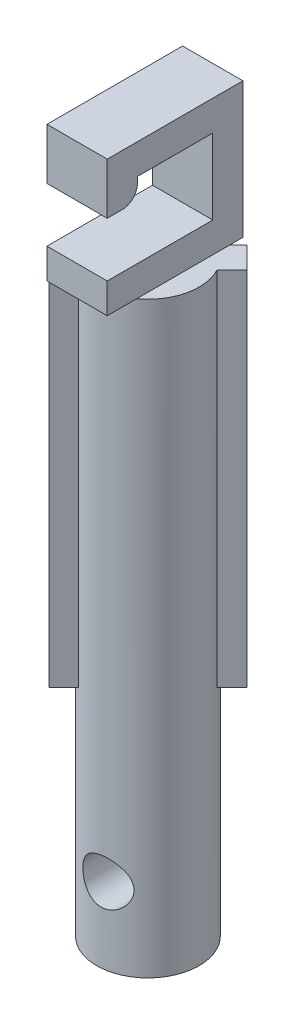
SolidWorks part; units mm, degrees
material "Plain Carbon Steel"
ref_plane "Front Plane" through (0, 0, 0) normal (0, 0, 1) x (1, 0, 0)
ref_plane "Top Plane" through (0, 0, 0) normal (0, 1, 0) x (1, 0, 0)
ref_plane "Right Plane" through (0, 0, 0) normal (1, 0, 0) x (0, 0, -1)
sketch "Sketch1" plane through (0, 0, 0) normal (0, 1, 0) x (1, 0, 0)
  circle A0 centre (0, 0) radius 1.7
  dimension "D1" = 3.4
extrude "main shaft" add sketch "Sketch1" along normal mid plane 12
sketch "Sketch2" plane through (0, 6, 0) normal (0, 1, 0) x (1, 0, 0)
  line L0 (3.2385, 3.2385) -> (-4.1755, -4.1755) construction
  line L1 (-0.7954, -1.5025) -> (-1.2903, -1.9974)
  line L2 (-1.2903, -1.9974) -> (-1.9974, -1.2903)
  line L3 (-1.9974, -1.2903) -> (-1.5025, -0.7954)
  line L4 (-1.9627, 1.9627) -> (2.0335, -2.0335) construction
  line L5 (1.2903, 1.9974) -> (0.7954, 1.5025)
  line L6 (1.9974, 1.2903) -> (1.2903, 1.9974)
  line L7 (1.5025, 0.7954) -> (1.9974, 1.2903)
  arc A0 (-1.5025, -0.7954) -> (-0.7954, -1.5025) centre (0, 0) ccw
  arc A1 (0.7954, 1.5025) -> (1.5025, 0.7954) centre (0, 0) cw
  circle A2 centre (0, 0) radius 1.7 construction
  point P8 (-1.0428, -1.75)
  dimension "D1" = 1
  dimension "D2" = 0.7
extrude "guides" add sketch "Sketch2" against normal blind 12
sketch "Sketch21" plane through (0, 6, 0) normal (0, 1, 0) x (1, 0, 0)
  line L0 (0, 0) -> (0, -1.7) construction
  line L1 (-1, 2.15) -> (1, 2.15)
  line L2 (-1, 2.15) -> (-1, -2.35)
  line L3 (-1, -2.35) -> (1, -2.35)
  line L4 (1, 2.15) -> (1, -2.35)
  line L5 (-1, 2.15) -> (1, -2.35) construction
  line L6 (-1, -2.35) -> (1, 2.15) construction
  arc A0 (-0.7954, -1.5025) -> (1.5025, 0.7954) centre (0, 0) ccw construction
  point P0 (0, -0.1)
  dimension "D1" = 4.5
  dimension "D2" = 2
  dimension "D3" = 0.1
extrude "hook extrude" add sketch "Sketch21" along normal blind 4.5
sketch "Sketch22" plane through (1, 0, 0) normal (1, 0, 0) x (0, 0, -1)
  line L0 (0.7954, 6) -> (-1.3748, 6) construction
  line L1 (1.15, 7) -> (44.9676, 7)
  line L2 (1.15, 7) -> (1.15, 9.5)
  line L3 (1.15, 9.5) -> (-1.35, 9.5)
  line L4 (-1.35, 8.8) -> (-1.35, 9.5)
  line L5 (1.15, 7) -> (-1.35, 9.5) construction
  line L6 (1.15, 9.5) -> (44.9676, 7) construction
  line L7 (-2.35, 10.5) -> (2.15, 10.5) construction
  line L8 (-1.35, 8.8) -> (-2.35, 8.8)
  line L9 (-2.35, 10.5) -> (-2.35, 6) construction
  line L10 (-2.35, 8.8) -> (-2.35, 7)
  line L11 (-2.35, 7) -> (44.9676, 7)
  point P0 (-1.5013, 9.6513)
  line M10 (-2.35, 10.5) -> (-2.35, 6)
  dimension "D1" = 2.5
  dimension "D2" = 1
  dimension "D3" = 1
  dimension "D4" = 1
  dimension "D5" = 0.7
extrude "hook cut" cut sketch "Sketch22" against normal through all contours L11 L2 L3 L4 L8 M10 region at (1, 8.1717, 0.4913)
fillet "hook fillet" radius 0.5 1 edges at (0, 8.8, 1.35)
sketch "Sketch23" plane through (0, -6, 0) normal (0, -1, 0) x (1, 0, 0)
  circle A0 centre (0, 0) radius 1.7
  dimension "D1" = 3.4
extrude "top stopper" add sketch "Sketch23" along normal blind 2
sketch "Sketch24" plane through (0, -8, 0) normal (0, -1, 0) x (1, 0, 0)
  circle A0 centre (0, 0) radius 1.7
  dimension "D1" = 3.4
extrude "bottom shaft" add sketch "Sketch24" along normal blind 5.5
ref_plane "Plane4" through (0, 0, 2.35) normal (0, 0, 1) x (1, 0, 0)
hole_wizard "Ø1.5mm Dowel Hole2" positions "Sketch27" profile "Sketch26" hole size "Ø1.5" standard "ISO" end condition through all
sketch "Sketch27" plane through (0, 0, 2.35) normal (0, 0, 1) x (1, 0, 0)
  line L0 (-1.7, -13.5) -> (1.7, -13.5) construction
  line L1 (-1.7, 6) -> (-1.7, -13.5) construction
  point P0 (0.2, -11)
  dimension "D1" = 2.5
  dimension "D2" = 1.9
sketch "Sketch26" plane through (0.2, -11, 2.35) normal (1, 0, 0) x (0, -1, 0)
  line L0 (0, 0) -> (0, 4.5)
  line L1 (0, 4.5) -> (0.75, 4.5)
  line L2 (0.75, 4.5) -> (0.75, 0)
  line L5 (0.75, 0) -> (0, 0)
  line L11 (0, -6.35) -> (0, 107.95) construction
  dimension "Thru Hole Dia." = 1.5
  dimension "Thru Hole Depth" = 4.5
